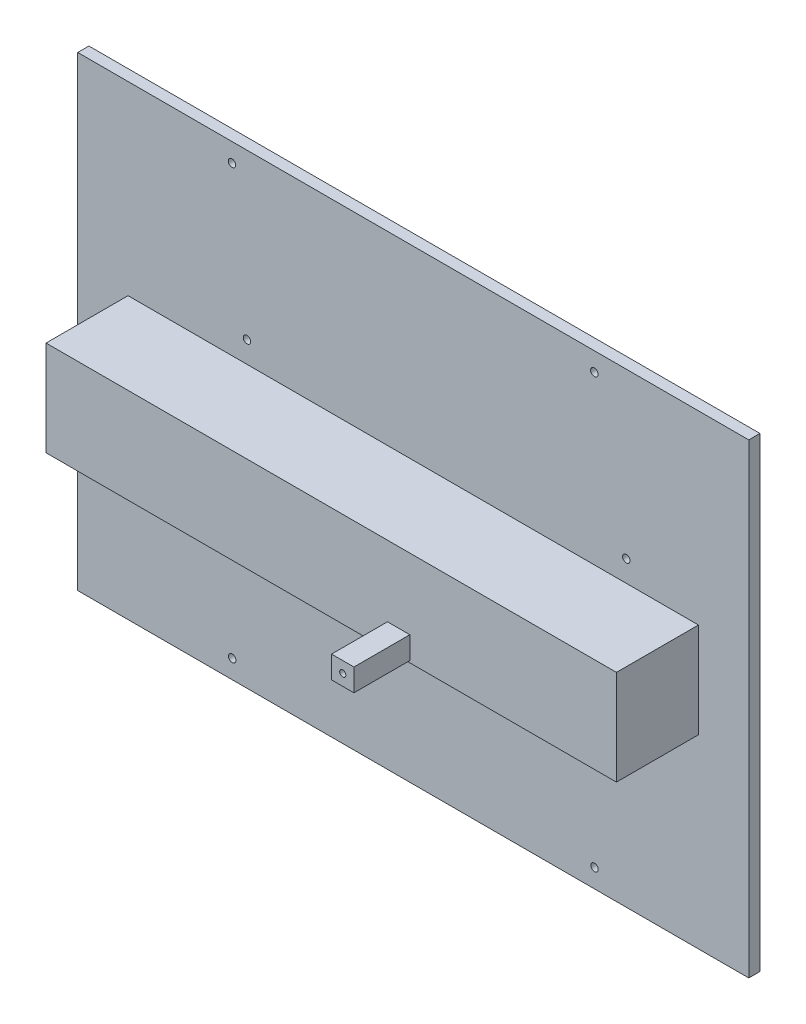
SolidWorks part; units mm, degrees
ref_plane "前视基准面" through (0, 0, 0) normal (0, 0, 1) x (1, 0, 0)
ref_plane "上视基准面" through (0, 0, 0) normal (0, 1, 0) x (1, 0, 0)
ref_plane "右视基准面" through (0, 0, 0) normal (1, 0, 0) x (0, 0, -1)
sketch "草图1" plane through (0, 0, 0) normal (0, 0, 1) x (1, 0, 0)
  line L1 (-90, 62.5) -> (90, 62.5)
  line L2 (-90, 62.5) -> (-90, -62.5)
  line L3 (-90, -62.5) -> (90, -62.5)
  line L4 (90, 62.5) -> (90, -62.5)
  line L5 (-90, 62.5) -> (90, -62.5) construction
  line L6 (-90, -62.5) -> (90, 62.5) construction
  point P0 (0, 0)
  dimension "D1" = 125
  dimension "D2" = 180
extrude "凸台-拉伸1" add sketch "草图1" along normal blind 3
sketch "草图7" plane through (0, 0, 0) normal (0, 0, -1) x (-1, 0, 0)
  line L1 (-74, 10.25) -> (74, 10.25)
  line L2 (-74, 10.25) -> (-74, -10.25)
  line L3 (-74, -10.25) -> (74, -10.25)
  line L4 (74, 10.25) -> (74, -10.25)
  line L5 (0, 0) -> (72.729, 0) construction
  line L8 (0, 0) -> (0, -50.9103) construction
  dimension "D1" = 20.5
  dimension "D2" = 148
extrude "电池位切除-拉伸3" cut sketch "草图7" against normal up to next
sketch "草图8" plane through (0, 0, 3) normal (0, 0, 1) x (1, 0, 0)
  line L12 (74, 10.25) -> (74, -10.25) construction
  line L13 (-76.5, 12.75) -> (76.5, 12.75)
  line L14 (-76.5, 12.75) -> (-76.5, -12.75)
  line L15 (-76.5, -12.75) -> (76.5, -12.75)
  line L16 (76.5, 12.75) -> (76.5, -12.75)
  line L17 (-74, -10.25) -> (-74, 10.25) construction
  line L18 (-74, 10.25) -> (74, 10.25) construction
  line L19 (74, -10.25) -> (-74, -10.25) construction
  line L20 (-74, 10.25) -> (74, 10.25)
  line L21 (74, -10.25) -> (-74, -10.25)
  line L22 (74, 10.25) -> (74, -10.25)
  line L23 (-74, -10.25) -> (-74, 10.25) construction
  line L24 (-74, -10.25) -> (-74, 10.25)
  dimension "D1" = 2.5
  dimension "D2" = 2.5
  dimension "D3" = 2.5
  dimension "D4" = 2.5
extrude "凸台-拉伸2" add sketch "草图8" along normal blind 22
sketch "草图9" plane through (0, 0, 25) normal (0, 0, 1) x (1, 0, 0)
  line L0 (76.5, 12.75) -> (-76.5, 12.75) construction
  line L5 (76.5, 12.75) -> (-76.5, 12.75)
  line L6 (-76.5, -12.75) -> (76.5, -12.75) construction
  line L7 (-76.5, -12.75) -> (76.5, -12.75)
  line L8 (76.5, -12.75) -> (76.5, 12.75) construction
  line L9 (76.5, -12.75) -> (76.5, 12.75)
  line L10 (-76.5, 12.75) -> (-76.5, -12.75) construction
  line L11 (-76.5, 12.75) -> (-76.5, -12.75)
extrude "凸台-拉伸3" add sketch "草图9" against normal blind 2.5
sketch "草图4" plane through (0, 0, 0) normal (0, 0, -1) x (-1, 0, 0)
  line L0 (74, -10.25) -> (74, 10.25) construction
  line L5 (74, 0) -> (84.6307, 0) construction
  line L10 (83.2374, -53.4277) -> (79.3374, -53.4277) construction
  line L11 (83.2374, -49.6277) -> (83.2374, -53.4277) construction
  line L12 (79.3374, -49.6277) -> (83.2374, -49.6277) construction
  line L29 (74, -4) -> (78, -4)
  line L30 (78, -4) -> (78, 4)
  line L31 (78, 4) -> (74, 4)
  line L32 (74, 4) -> (74, -4)
  dimension "D1" = 8
  dimension "D2" = 4
extrude "切除-拉伸2" cut sketch "草图4" along normal blind 1.6 from surface starting at face at (0, 0, 3)
sketch "草图10" plane through (0, 0, 25) normal (0, 0, 1) x (1, 0, 0)
  line L0 (18.0886, -9.21) -> (8.5541, -9.21) construction
  line L2 (15.0886, -6.21) -> (15.0886, -12.21)
  line L4 (21.0886, -6.21) -> (21.0886, -12.21)
  line L5 (18.0886, -9.21) -> (18.0886, -3.21) construction
  line L6 (0, 0) -> (60.8594, 0) construction
  line L7 (0, 0) -> (0, 60.5) construction
  line L8 (75, 60.5) -> (-75, 60.5) construction
  line L9 (15.0886, -6.21) -> (21.0886, -6.21)
  line L10 (15.0886, -12.21) -> (21.0886, -12.21)
  circle A0 centre (18.0886, -9.21) radius 0.825
  dimension "D2" = 1.65
  dimension "D1" = 6
extrude "凸台-拉伸4" add sketch "草图10" along normal up to surface (15 mm away)
sketch "草图11" plane through (0, 0, 0) normal (0, 0, -1) x (-1, 0, 0)
  circle A0 centre (-48.6147, -57.5) radius 1 construction
  circle A1 centre (-44.6, -18.5) radius 1 construction
  circle A2 centre (57.15, -18.5) radius 1 construction
  circle A3 centre (48.5747, -57.5) radius 1 construction
  circle A5 centre (48.6147, 57.5) radius 1 construction
  circle A6 centre (-57.15, 18.5) radius 1 construction
  circle A7 centre (-48.5747, 57.5) radius 1 construction
  circle A8 centre (-48.6147, -57.5) radius 1
  circle A9 centre (-44.6, -18.5) radius 1
  circle A10 centre (57.15, -18.5) radius 1
  circle A11 centre (48.5747, -57.5) radius 1
  circle A13 centre (48.6147, 57.5) radius 1
  circle A14 centre (-57.15, 18.5) radius 1
  circle A15 centre (-48.5747, 57.5) radius 1
  circle A16 centre (44.6, 18.5) radius 1 construction
  circle A17 centre (44.6, 18.5) radius 1
extrude "切除-拉伸3" cut sketch "草图11" against normal up to next
sketch "草图12" plane through (0, 0, 0) normal (0, 0, -1) x (-1, 0, 0)
  circle A0 centre (-48.5747, 57.5) radius 2
  circle A1 centre (-57.15, 18.5) radius 2
  circle A2 centre (-44.6, -18.5) radius 2
  circle A3 centre (-48.6147, -57.5) radius 2
  circle A4 centre (48.5747, -57.5) radius 2
  circle A5 centre (57.15, -18.5) radius 2
  circle A8 centre (48.6147, 57.5) radius 2
  circle A9 centre (44.6, 18.5) radius 2
  dimension "D1" = 4
extrude "切除-拉伸4" cut sketch "草图12" against normal blind 1.2
